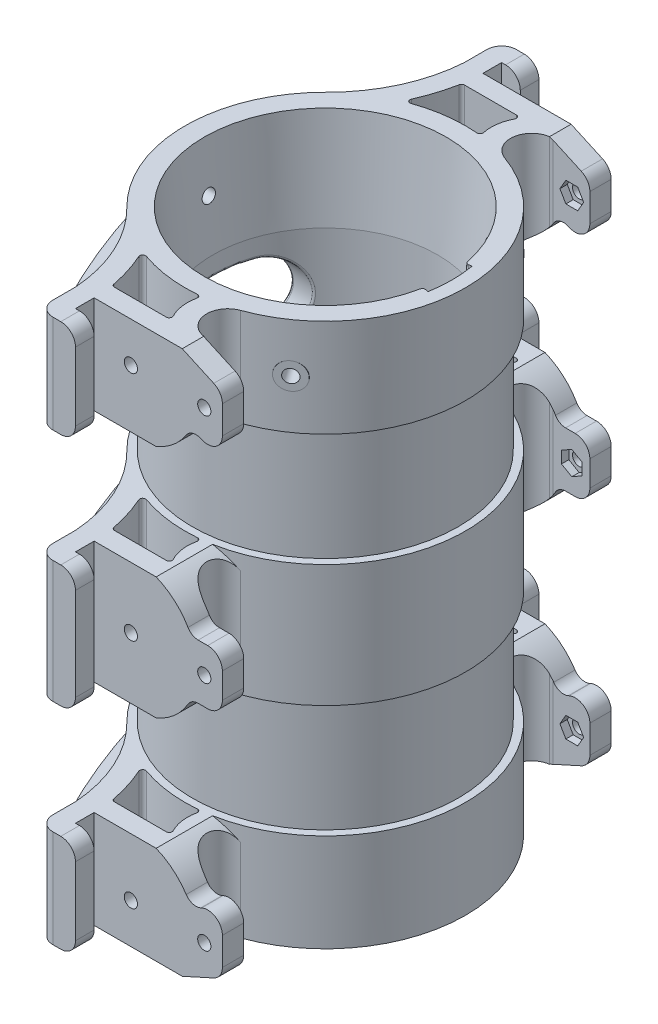
SolidWorks part; units mm, degrees
ref_plane "Front Plane" through (0, 0, 0) normal (0, 0, 1) x (1, 0, 0)
ref_plane "Top Plane" through (0, 0, 0) normal (0, 1, 0) x (1, 0, 0)
ref_plane "Right Plane" through (0, 0, 0) normal (1, 0, 0) x (0, 0, -1)
sketch "Sketch1" plane through (0, 0, 0) normal (0, 1, 0) x (1, 0, 0)
  line L0 (0, 38.25) -> (0, 45.25) construction
  circle A0 centre (0, 0) radius 38.25
  circle A1 centre (0, 0) radius 45.25
  dimension "D1" = 76.5
  dimension "D2" = 7
extrude "Boss-Extrude1" add sketch "Sketch1" along normal mid plane 185
sketch "Sketch2" plane through (0, -92.5, 0) normal (0, -1, 0) x (1, 0, 0)
  line L0 (0, 36.25) -> (0, 38.25) construction
  circle A0 centre (0, 0) radius 36.25
  circle A1 centre (0, 0) radius 38.25 construction
  circle A2 centre (0, 0) radius 38.25
  dimension "D1" = 2
extrude "Boss-Extrude2" add sketch "Sketch2" against normal blind 100 from offset 6.35 offset against normal yes
sketch "Sketch7" plane through (0, 0, 0) normal (1, 0, 0) x (0, 0, -1)
  line L0 (45.25, 92.5) -> (-45.25, 92.5) construction
  line L1 (12.5, 40) -> (-12.5, 40) construction
  line L2 (12.5, 27.5) -> (-12.5, 27.5)
  line L3 (12.5, 52.5) -> (-12.5, 52.5)
  circle A0 centre (0, 40) radius 12.5 construction
  arc A1 (12.5, 27.5) -> (12.5, 52.5) centre (12.5, 40) ccw
  arc A2 (-12.5, 52.5) -> (-12.5, 27.5) centre (-12.5, 40) ccw
  point P7 (0, 40)
  dimension "D2" = 25
  dimension "D3" = 25
  dimension "D1" = 52.5
extrude "Cut-Extrude4" cut sketch "Sketch7" against normal through all
sketch "Sketch8" plane through (0, 0, 0) normal (0, 1, 0) x (1, 0, 0)
  line L1 (17.5, -66.175) -> (128.1882, -66.175) construction
  line L2 (-18.85, -66.175) -> (-18.85, -78.875)
  line L3 (-18.85, -78.875) -> (-6.15, -78.875)
  line L4 (45.25, 0) -> (-45.25, 0) construction
  line L5 (31.75, 0) -> (50, 0) construction
  line L6 (-6.15, -78.875) -> (-6.15, -72.525)
  line L7 (-12.5, -72.525) -> (17.5, -72.525) construction
  line L8 (-6.15, -72.525) -> (-12.5, -72.525)
  line L9 (-12.5, -72.525) -> (-12.5, -66.175)
  line L10 (-12.5, -66.175) -> (43.65, -66.175)
  line L11 (-12.5, 66.175) -> (43.65, 66.175)
  line L12 (-12.5, 72.525) -> (-12.5, 66.175)
  line L13 (-6.15, 72.525) -> (-12.5, 72.525)
  line L14 (-6.15, 78.875) -> (-6.15, 72.525)
  line L15 (-18.85, 78.875) -> (-6.15, 78.875)
  line L16 (-18.85, 66.175) -> (-18.85, 78.875)
  line L18 (43.65, -66.175) -> (43.65, -58.9107)
  line L19 (43.65, -58.9107) -> (18.65, -58.9107)
  line L20 (43.65, 58.9107) -> (18.65, 58.9107)
  line L21 (43.65, 66.175) -> (43.65, 58.9107)
  line L22 (-12.5, -72.525) -> (-18.85, -72.525) construction
  arc A0 (-32.8241, -31.1471) -> (-18.85, -66.175) centre (-69.7381, -66.175) cw
  circle A1 centre (0, 0) radius 45.25 construction
  arc A2 (-32.8241, -31.1471) -> (15.7007, -42.4388) centre (0, 0) ccw
  arc A3 (-32.8241, 31.1471) -> (15.7007, 42.4388) centre (0, 0) cw
  arc A4 (-32.8241, 31.1471) -> (-18.85, 66.175) centre (-69.7381, 66.175) ccw
  arc A9 (18.65, -58.9107) -> (15.7007, -42.4388) centre (18.65, -50.4107) cw
  arc A10 (18.65, 58.9107) -> (15.7007, 42.4388) centre (18.65, 50.4107) ccw
  dimension "D1" = 8.5
  dimension "D2" = 62.5
  dimension "D3" = 25
extrude "Boss-Extrude3" add sketch "Sketch8" along normal up to surface and the other way up to surface up to face at (0, 92.5, 45.25) other way up to face at (0, -92.5, 45.25)
sketch "Sketch10" plane through (0, 0, 66.175) normal (0, 0, 1) x (1, 0, 0)
  line L0 (17.5, -92.5) -> (43.65, -92.5)
  line L1 (43.65, -92.5) -> (43.65, -80.6536)
  line L2 (-6.15, -59.2129) -> (-32.8241, -59.2129)
  line L3 (128.1882, -42.3564) -> (17.5, -92.5) construction
  line L4 (43.65, -80.6536) -> (17.5, -92.5)
  line L5 (43.65, 80.6536) -> (43.65, 92.5)
  line L6 (17.5, 92.5) -> (128.1882, 42.3564) construction
  line L7 (43.65, 92.5) -> (17.5, 92.5)
  line L8 (-12.5, 92.5) -> (43.65, 92.5) construction
  line L9 (17.5, 92.5) -> (43.65, 80.6536)
  line L10 (43.65, -60.1882) -> (43.65, -9.3209)
  line L11 (79.953, -43.7423) -> (23.8431, -69.161) construction
  line L12 (22.9086, -9.3209) -> (60.2886, -9.3209) construction
  line L21 (22.9086, -9.3209) -> (43.65, -9.3209)
  line L23 (43.65, -60.1882) -> (23.8431, -69.161)
  line L25 (-6.15, 92.5) -> (-6.15, -92.5) construction
  line L26 (-32.8241, 92.5) -> (-32.8241, -92.5) construction
  line L32 (-32.8241, -59.2129) -> (-32.8241, -20.7871)
  line L36 (-32.8241, -20.7871) -> (-6.15, -20.7871)
  line L40 (0, 0) -> (-32.8241, 0) construction
  line L45 (8.611, -59.2129) -> (-6.15, -59.2129)
  line L46 (8.611, -20.7871) -> (-6.15, -20.7871)
  line L47 (-32.8241, 59.2129) -> (-32.8241, 20.7871)
  line L48 (-6.15, 59.2129) -> (-32.8241, 59.2129)
  line L49 (8.611, 59.2129) -> (-6.15, 59.2129)
  line L50 (43.65, 60.1882) -> (23.8431, 69.161)
  line L51 (43.65, 60.1882) -> (43.65, 9.3209)
  line L52 (22.9086, 9.3209) -> (43.65, 9.3209)
  line L53 (8.611, 20.7871) -> (-6.15, 20.7871)
  line L54 (-32.8241, 20.7871) -> (-6.15, 20.7871)
  line L55 (43.65, 92.5) -> (43.65, -92.5) construction
  arc A6 (18.8427, -67.7035) -> (23.8431, -69.161) centre (22.1925, -65.5175) ccw construction
  arc A7 (18.8427, -67.7035) -> (8.611, -59.2129) centre (0, -80) ccw construction
  arc A10 (8.611, -20.7871) -> (19.4507, -11.3102) centre (0, 0) ccw construction
  arc A11 (22.9086, -9.3209) -> (19.4507, -11.3102) centre (22.9086, -13.3209) ccw construction
  arc A18 (18.8427, -67.7035) -> (23.8431, -69.161) centre (22.1925, -65.5175) ccw
  arc A19 (18.8427, -67.7035) -> (8.611, -59.2129) centre (0, -80) ccw
  arc A22 (8.611, -20.7871) -> (19.4507, -11.3102) centre (0, 0) ccw
  arc A23 (22.9086, -9.3209) -> (19.4507, -11.3102) centre (22.9086, -13.3209) ccw
  arc A24 (18.8427, 67.7035) -> (8.611, 59.2129) centre (0, 80) cw
  arc A25 (18.8427, 67.7035) -> (23.8431, 69.161) centre (22.1925, 65.5175) cw
  arc A26 (22.9086, 9.3209) -> (19.4507, 11.3102) centre (22.9086, 13.3209) cw
  arc A27 (8.611, 20.7871) -> (19.4507, 11.3102) centre (0, 0) cw
extrude "Cut-Extrude6" cut sketch "Sketch10" against normal up to surface and the other way through all up to face at (-41.5057, 40, 0)
sketch "Sketch11" plane through (0, 0, -78.875) normal (0, 0, -1) x (-1, 0, 0)
  line L3 (-43.65, 92.5) -> (-43.65, 80.6536)
  line L4 (-17.5, 92.5) -> (-43.65, 92.5)
  line L5 (-43.65, 80.6536) -> (-17.5, 92.5)
  line L6 (-43.65, 92.5) -> (-43.65, 80.6536)
  line L7 (-17.5, 92.5) -> (-43.65, 92.5)
  line L8 (-43.65, 80.6536) -> (-17.5, 92.5)
  line L9 (-43.65, -92.5) -> (-17.5, -92.5)
  line L10 (-43.65, -80.6536) -> (-43.65, -92.5)
  line L11 (-17.5, -92.5) -> (-43.65, -80.6536)
  line L12 (-43.65, -92.5) -> (-17.5, -92.5)
  line L13 (-43.65, -80.6536) -> (-43.65, -92.5)
  line L14 (-17.5, -92.5) -> (-43.65, -80.6536)
  line L20 (32.8241, 20.7871) -> (32.8241, 59.2129)
  line L21 (6.15, 20.7871) -> (32.8241, 20.7871)
  line L22 (-8.611, 20.7871) -> (6.15, 20.7871)
  line L23 (-43.65, 9.3209) -> (-22.9086, 9.3209)
  line L24 (-43.65, 60.1882) -> (-43.65, 9.3209)
  line L25 (-23.8431, 69.161) -> (-43.65, 60.1882)
  line L26 (6.15, 59.2129) -> (-8.611, 59.2129)
  line L27 (32.8241, 59.2129) -> (6.15, 59.2129)
  line L28 (32.8241, 20.7871) -> (32.8241, 59.2129)
  line L29 (6.15, 20.7871) -> (32.8241, 20.7871)
  line L30 (-8.611, 20.7871) -> (6.15, 20.7871)
  line L31 (-43.65, 9.3209) -> (-22.9086, 9.3209)
  line L32 (-43.65, 60.1882) -> (-43.65, 9.3209)
  line L33 (-23.8431, 69.161) -> (-43.65, 60.1882)
  line L34 (6.15, 59.2129) -> (-8.611, 59.2129)
  line L35 (32.8241, 59.2129) -> (6.15, 59.2129)
  line L36 (-22.9086, -9.3209) -> (-43.65, -9.3209)
  line L37 (-43.65, -9.3209) -> (-43.65, -60.1882)
  line L38 (-43.65, -60.1882) -> (-23.8431, -69.161)
  line L39 (-8.611, -59.2129) -> (6.15, -59.2129)
  line L40 (6.15, -59.2129) -> (32.8241, -59.2129)
  line L41 (32.8241, -59.2129) -> (32.8241, -20.7871)
  line L42 (32.8241, -20.7871) -> (6.15, -20.7871)
  line L43 (6.15, -20.7871) -> (-8.611, -20.7871)
  line L44 (-22.9086, -9.3209) -> (-43.65, -9.3209)
  line L45 (-43.65, -9.3209) -> (-43.65, -60.1882)
  line L46 (-43.65, -60.1882) -> (-23.8431, -69.161)
  line L47 (-8.611, -59.2129) -> (6.15, -59.2129)
  line L48 (6.15, -59.2129) -> (32.8241, -59.2129)
  line L49 (32.8241, -59.2129) -> (32.8241, -20.7871)
  line L50 (32.8241, -20.7871) -> (6.15, -20.7871)
  line L51 (6.15, -20.7871) -> (-8.611, -20.7871)
  arc A4 (-8.611, 20.7871) -> (-19.4507, 11.3102) centre (0, 0) ccw
  arc A5 (-22.9086, 9.3209) -> (-19.4507, 11.3102) centre (-22.9086, 13.3209) ccw
  arc A6 (-18.8427, 67.7035) -> (-23.8431, 69.161) centre (-22.1925, 65.5175) ccw
  arc A7 (-18.8427, 67.7035) -> (-8.611, 59.2129) centre (0, 80) ccw
  arc A8 (-8.611, 20.7871) -> (-19.4507, 11.3102) centre (0, 0) ccw
  arc A9 (-22.9086, 9.3209) -> (-19.4507, 11.3102) centre (-22.9086, 13.3209) ccw
  arc A10 (-18.8427, 67.7035) -> (-23.8431, 69.161) centre (-22.1925, 65.5175) ccw
  arc A11 (-18.8427, 67.7035) -> (-8.611, 59.2129) centre (0, 80) ccw
  arc A12 (-23.8431, -69.161) -> (-18.8427, -67.7035) centre (-22.1925, -65.5175) ccw
  arc A13 (-8.611, -59.2129) -> (-18.8427, -67.7035) centre (0, -80) ccw
  arc A14 (-19.4507, -11.3102) -> (-8.611, -20.7871) centre (0, 0) ccw
  arc A15 (-19.4507, -11.3102) -> (-22.9086, -9.3209) centre (-22.9086, -13.3209) ccw
  arc A16 (-23.8431, -69.161) -> (-18.8427, -67.7035) centre (-22.1925, -65.5175) ccw
  arc A17 (-8.611, -59.2129) -> (-18.8427, -67.7035) centre (0, -80) ccw
  arc A18 (-19.4507, -11.3102) -> (-8.611, -20.7871) centre (0, 0) ccw
  arc A19 (-19.4507, -11.3102) -> (-22.9086, -9.3209) centre (-22.9086, -13.3209) ccw
  dimension "D1" = 0
  dimension "D2" = 0
  dimension "D3" = 0
  dimension "D4" = 0
extrude "Cut-Extrude7" cut sketch "Sketch11" against normal up to surface (66.9486 mm away) up to face at (-3.9052, 0.3336, 17.6166)
fillet "Fillet5" radius 5 6 edges at (-18.85, -75.8565, -78.875) (-18.85, 0, -78.875) (-18.85, 75.8565, -78.875) (-18.85, 0, 78.875) (-18.85, -75.8565, 78.875) (-18.85, 75.8565, 78.875)
sketch "Sketch14" plane through (0, 0, -66.175) normal (0, 0, -1) x (-1, 0, 0)
  line L0 (0, 0) -> (-25, 0) construction
  line L5 (-25, 78.8696) -> (-25, 0) construction
  circle A3 centre (-25, 78.8696) radius 2.25
  circle A5 centre (-25, 0) radius 2.25
  circle A7 centre (-25, -78.8696) radius 2.25
  circle A8 centre (0, 0) radius 2.25
  circle A9 centre (0, 78.8696) radius 2.25
  circle A10 centre (0, -78.8696) radius 2.25
  dimension "D1" = 25
  dimension "D2" = 78.8696
  dimension "D3" = 4.5
extrude "Cut-Extrude8" cut sketch "Sketch14" against normal up to surface (7.2643 mm away) up to face at (27.8361, -73.0039, -58.9107)
sketch "Sketch15" plane through (0, 0, 66.175) normal (0, 0, 1) x (1, 0, 0)
  circle A1 centre (0, -78.8696) radius 2.25
  circle A3 centre (0, -78.8696) radius 2.25
  circle A5 centre (0, 78.8696) radius 2.25
  circle A7 centre (0, 78.8696) radius 2.25
  circle A9 centre (0, 0) radius 2.25
  circle A11 centre (0, 0) radius 2.25
  circle A13 centre (25, 78.8696) radius 2.25
  circle A14 centre (25, 78.8696) radius 2.25
  circle A15 centre (25, -78.8696) radius 2.25
  circle A16 centre (25, -78.8696) radius 2.25
  circle A17 centre (25, 0) radius 2.25
  circle A18 centre (25, 0) radius 2.25
  dimension "D1" = 0
  dimension "D2" = 0
  dimension "D3" = 0
  dimension "D4" = 0
  dimension "D5" = 0
  dimension "D6" = 0
extrude "Cut-Extrude9" cut sketch "Sketch15" against normal up to surface (7.2643 mm away) up to face at (27.8361, -73.0039, 58.9107)
sketch "Sketch16" plane through (0, 92.5, 0) normal (0, 1, 0) x (1, 0, 0)
  line L0 (-45.25, 0) -> (-47.75, 0) construction
  circle A0 centre (0, 0) radius 47.75
  circle A1 centre (0, 0) radius 45.25
  arc A2 (-32.8241, 31.1471) -> (-32.8241, -31.1471) centre (0, 0) ccw construction
  dimension "D1" = 2.5
extrude "Boss-Extrude4" add sketch "Sketch16" against normal up to surface (33.2871 mm away) up to face at (-10.3824, 59.2129, 65.577)
sketch "Sketch17" plane through (0, -92.5, 0) normal (0, -1, 0) x (1, 0, 0)
  circle A1 centre (0, 0) radius 45.25
  circle A2 centre (0, 0) radius 45.25
  circle A3 centre (0, 0) radius 47.75
  circle A4 centre (0, 0) radius 47.75
  dimension "D1" = 0
  dimension "D2" = 0
extrude "Boss-Extrude5" add sketch "Sketch17" against normal up to surface (33.2871 mm away) up to face at (-10.3824, -59.2129, 65.577)
sketch "Sketch18" plane through (0, -20.7871, 0) normal (0, -1, 0) x (1, 0, 0)
  circle A1 centre (0, 0) radius 47.75
  circle A2 centre (0, 0) radius 47.75
  circle A3 centre (0, 0) radius 45.25
  circle A4 centre (0, 0) radius 45.25
  dimension "D1" = 0
  dimension "D2" = 0
extrude "Boss-Extrude6" add sketch "Sketch18" against normal up to surface (41.5741 mm away) up to face at (-10.3824, 20.7871, 65.577)
sketch "Sketch20" plane through (0, 0, 0) normal (1, 0, 0) x (0, 0, -1)
  line L0 (-45.25, -20.7871) -> (45.25, -20.7871) construction
  line L1 (46.9672, -59.2129) -> (-46.9672, -59.2129) construction
  line L2 (-45.25, 59.2129) -> (45.25, 59.2129) construction
  line L3 (46.9672, 20.7871) -> (-46.9672, 20.7871) construction
  line L4 (-45.25, -20.7871) -> (45.25, -20.7871) construction
  line L5 (46.9672, -59.2129) -> (-46.9672, -59.2129) construction
  line L6 (-45.25, 59.2129) -> (45.25, 59.2129) construction
  line L7 (46.9672, 20.7871) -> (-46.9672, 20.7871) construction
  line L8 (0, -20.7871) -> (0, -59.2129) construction
  line L9 (0, 59.2129) -> (0, 20.7871) construction
  line L10 (-10, 40) -> (10, 40) construction
  line L11 (-10, 45) -> (10, 45)
  line L12 (-10, 35) -> (10, 35)
  line L13 (0, 0) -> (46.4328, 0) construction
  line L14 (46.4328, 19.5496) -> (46.4328, -19.5496) construction
  line L15 (-10, -40) -> (10, -40) construction
  line L16 (-10, -45) -> (10, -45)
  line L17 (-10, -35) -> (10, -35)
  arc A2 (-10, 45) -> (-10, 35) centre (-10, 40) ccw
  arc A3 (10, 35) -> (10, 45) centre (10, 40) ccw
  arc A4 (-10, -45) -> (-10, -35) centre (-10, -40) cw
  arc A5 (10, -35) -> (10, -45) centre (10, -40) cw
  point P2 (0, 40)
  point P14 (0, -20.7871)
  point P30 (0, -40)
  dimension "D1" = 20
  dimension "D2" = 5
extrude "Cut-Extrude10" [suppressed] cut sketch "Sketch20" along normal through all
pattern_circular "CirPattern1" [suppressed] count 6 over 360 reverse direction yes of bodies 118
ref_plane "Plane1" through (-26.1107, -92.5, 39.9787) normal (0, -1, 0) x (-1, 0, 0)
sketch "Sketch23" plane through (0, -92.5, 0) normal (0, -1, 0) x (1, 0, 0)
  line L0 (0, 0) -> (-47.75, 0) construction
  arc A0 (-18.85, 66.175) -> (-33.5786, 33.9491) centre (-68.7395, 69.4978) cw
  arc A1 (-26.1107, 39.9787) -> (-26.1107, -39.9787) centre (0, 0) ccw construction
  arc A2 (-33.5786, 33.9491) -> (-26.1107, 39.9787) centre (0, 0) cw
  arc A3 (-18.85, 66.175) -> (-26.1107, 39.9787) centre (-69.7381, 66.175) cw
  arc A4 (-18.85, -66.175) -> (-26.1107, -39.9787) centre (-69.7381, -66.175) ccw
  arc A5 (-33.5786, -33.9491) -> (-26.1107, -39.9787) centre (0, 0) ccw
  arc A6 (-18.85, -66.175) -> (-33.5786, -33.9491) centre (-68.7395, -69.4978) ccw
  arc A7 (-26.1107, 39.9787) -> (-18.85, 66.175) centre (-69.7381, 66.175) ccw construction
  dimension "D1" = 50
extrude "Boss-Extrude7" add sketch "Sketch23" against normal up to surface (33.2871 mm away) up to face at (-8.8243, -59.2129, 0)
sketch "Sketch24" plane through (0, 92.5, 0) normal (0, 1, 0) x (1, 0, 0)
  arc A3 (-26.1107, 39.9787) -> (-18.85, 66.175) centre (-69.7381, 66.175) ccw
  arc A4 (-26.1107, 39.9787) -> (-33.5786, 33.9491) centre (0, 0) ccw
  arc A5 (-33.5786, 33.9491) -> (-18.85, 66.175) centre (-68.7395, 69.4978) ccw
  arc A6 (-26.1107, 39.9787) -> (-18.85, 66.175) centre (-69.7381, 66.175) ccw
  arc A7 (-26.1107, 39.9787) -> (-33.5786, 33.9491) centre (0, 0) ccw
  arc A8 (-33.5786, 33.9491) -> (-18.85, 66.175) centre (-68.7395, 69.4978) ccw
  arc A9 (-18.85, -66.175) -> (-33.5786, -33.9491) centre (-68.7395, -69.4978) ccw
  arc A10 (-33.5786, -33.9491) -> (-26.1107, -39.9787) centre (0, 0) ccw
  arc A11 (-18.85, -66.175) -> (-26.1107, -39.9787) centre (-69.7381, -66.175) ccw
  arc A12 (-18.85, -66.175) -> (-33.5786, -33.9491) centre (-68.7395, -69.4978) ccw
  arc A13 (-33.5786, -33.9491) -> (-26.1107, -39.9787) centre (0, 0) ccw
  arc A14 (-18.85, -66.175) -> (-26.1107, -39.9787) centre (-69.7381, -66.175) ccw
  dimension "D1" = 0
  dimension "D2" = 0
extrude "Boss-Extrude8" add sketch "Sketch24" against normal up to surface (33.2871 mm away) up to face at (-45.25, 59.2129, 0)
sketch "Sketch25" plane through (0, 20.7871, 0) normal (0, 1, 0) x (1, 0, 0)
  arc A3 (-18.85, -66.175) -> (-33.5786, -33.9491) centre (-68.7395, -69.4978) ccw
  arc A4 (-33.5786, -33.9491) -> (-26.1107, -39.9787) centre (0, 0) ccw
  arc A5 (-18.85, -66.175) -> (-26.1107, -39.9787) centre (-69.7381, -66.175) ccw
  arc A6 (-18.85, -66.175) -> (-33.5786, -33.9491) centre (-68.7395, -69.4978) ccw
  arc A7 (-33.5786, -33.9491) -> (-26.1107, -39.9787) centre (0, 0) ccw
  arc A8 (-18.85, -66.175) -> (-26.1107, -39.9787) centre (-69.7381, -66.175) ccw
  arc A9 (-26.1107, 39.9787) -> (-18.85, 66.175) centre (-69.7381, 66.175) ccw
  arc A10 (-33.5786, 33.9491) -> (-18.85, 66.175) centre (-68.7395, 69.4978) ccw
  arc A11 (-26.1107, 39.9787) -> (-33.5786, 33.9491) centre (0, 0) ccw
  arc A12 (-26.1107, 39.9787) -> (-18.85, 66.175) centre (-69.7381, 66.175) ccw
  arc A13 (-33.5786, 33.9491) -> (-18.85, 66.175) centre (-68.7395, 69.4978) ccw
  arc A14 (-26.1107, 39.9787) -> (-33.5786, 33.9491) centre (0, 0) ccw
  dimension "D1" = 0
  dimension "D2" = 0
extrude "Boss-Extrude9" add sketch "Sketch25" against normal up to surface (41.5741 mm away) up to face at (-45.25, -20.7871, 0)
sketch "Sketch27" plane through (0, 0, 0) normal (0, 0, 1) x (1, 0, 0)
  line L0 (38.25, 59.2129) -> (41.1622, 92.5)
  line L3 (38.25, 59.2129) -> (0, 59.2129) construction
  line L5 (-18.85, 92.5) -> (-33.5786, 92.5) construction
  line L6 (38.25, 59.2129) -> (38.25, 92.5)
  line L7 (38.25, 92.5) -> (41.1622, 92.5)
  line L8 (0, 59.2129) -> (0, 92.5) construction
  dimension "D1" = 33.2871
  dimension "D2" = 5
  dimension "D3" = 38.25
  dimension "D4" = 38.25
  dimension "D5" = 38.25
revolve "Cut-Revolve1" cut sketch "Sketch27" angle 360 about L8
sketch "Sketch28" plane through (0, 92.5, 0) normal (0, 1, 0) x (1, 0, 0)
  line L1 (43.65, 58.9107) -> (18.65, 58.9107) construction
  line L2 (0, 0) -> (47.75, 0) construction
  line L3 (11.1383, 46.4328) -> (10.15, 46.6698)
  line L4 (10.15, 46.6698) -> (10.15, 58.8326)
  line L5 (10.15, 58.8326) -> (17.5, 58.8326)
  line L6 (10.15, -58.8326) -> (17.5, -58.8326)
  line L7 (10.15, -46.6698) -> (10.15, -58.8326)
  line L8 (11.1383, -46.4328) -> (10.15, -46.6698)
  arc A0 (17.5, 58.8326) -> (16.1276, 44.944) centre (18.5576, 51.716) ccw
  arc A1 (11.1383, -46.4328) -> (11.1383, 46.4328) centre (0, 0) ccw construction
  arc A2 (16.1276, 44.944) -> (11.1383, 46.4328) centre (0, 0) ccw
  arc A7 (17.5, 58.8326) -> (11.1383, 46.4328) centre (18.65, 50.4107) ccw construction
  arc A8 (16.1276, -44.944) -> (11.1383, -46.4328) centre (0, 0) cw
  arc A9 (17.5, -58.8326) -> (16.1276, -44.944) centre (18.5576, -51.716) cw
extrude "Boss-Extrude13" add sketch "Sketch28" against normal up to surface (26.6421 mm away) up to face at (13.4579, 62.8457, 57.713)
sketch "Sketch29" plane through (0, -92.5, 0) normal (0, -1, 0) x (1, 0, 0)
  line L3 (11.1383, -46.4328) -> (10.15, -46.6698)
  line L4 (10.15, -46.6698) -> (10.15, -58.8326)
  line L5 (10.15, -58.8326) -> (17.5, -58.8326)
  line L6 (11.1383, -46.4328) -> (10.15, -46.6698)
  line L7 (10.15, -46.6698) -> (10.15, -58.8326)
  line L8 (10.15, -58.8326) -> (17.5, -58.8326)
  line L9 (17.5, 58.8326) -> (10.15, 58.8326)
  line L10 (10.15, 46.6698) -> (11.1383, 46.4328)
  line L11 (10.15, 58.8326) -> (10.15, 46.6698)
  line L12 (17.5, 58.8326) -> (10.15, 58.8326)
  line L13 (10.15, 46.6698) -> (11.1383, 46.4328)
  line L14 (10.15, 58.8326) -> (10.15, 46.6698)
  arc A2 (16.1276, -44.944) -> (17.5, -58.8326) centre (18.5576, -51.716) ccw
  arc A3 (11.1383, -46.4328) -> (16.1276, -44.944) centre (0, 0) ccw
  arc A4 (16.1276, -44.944) -> (17.5, -58.8326) centre (18.5576, -51.716) ccw
  arc A5 (11.1383, -46.4328) -> (16.1276, -44.944) centre (0, 0) ccw
  arc A6 (17.5, 58.8326) -> (16.1276, 44.944) centre (18.5576, 51.716) ccw
  arc A7 (16.1276, 44.944) -> (11.1383, 46.4328) centre (0, 0) ccw
  arc A8 (17.5, 58.8326) -> (16.1276, 44.944) centre (18.5576, 51.716) ccw
  arc A9 (16.1276, 44.944) -> (11.1383, 46.4328) centre (0, 0) ccw
  dimension "D1" = 0
  dimension "D2" = 0
extrude "Boss-Extrude14" add sketch "Sketch29" against normal up to surface (32.0496 mm away) up to face at (13.7418, -62.9735, 57.3608)
sketch "Sketch30" plane through (0, 0, 0) normal (0, 1, 0) x (1, 0, 0)
  line L3 (10.15, 46.6698) -> (11.1383, 46.4328)
  line L4 (10.15, 58.8326) -> (10.15, 46.6698)
  line L5 (17.5, 58.8326) -> (10.15, 58.8326)
  line L6 (10.15, 46.6698) -> (11.1383, 46.4328)
  line L7 (10.15, 58.8326) -> (10.15, 46.6698)
  line L8 (17.5, 58.8326) -> (10.15, 58.8326)
  line L9 (10.15, -46.6698) -> (10.15, -58.8326)
  line L10 (10.15, -58.8326) -> (17.5, -58.8326)
  line L11 (11.1383, -46.4328) -> (10.15, -46.6698)
  line L12 (10.15, -46.6698) -> (10.15, -58.8326)
  line L13 (10.15, -58.8326) -> (17.5, -58.8326)
  line L14 (11.1383, -46.4328) -> (10.15, -46.6698)
  arc A2 (17.5, 58.8326) -> (16.1276, 44.944) centre (18.5576, 51.716) ccw
  arc A3 (16.1276, 44.944) -> (11.1383, 46.4328) centre (0, 0) ccw
  arc A4 (17.5, 58.8326) -> (16.1276, 44.944) centre (18.5576, 51.716) ccw
  arc A5 (16.1276, 44.944) -> (11.1383, 46.4328) centre (0, 0) ccw
  arc A6 (16.1276, -44.944) -> (17.5, -58.8326) centre (18.5576, -51.716) ccw
  arc A7 (11.1383, -46.4328) -> (16.1276, -44.944) centre (0, 0) ccw
  arc A8 (16.1276, -44.944) -> (17.5, -58.8326) centre (18.5576, -51.716) ccw
  arc A9 (11.1383, -46.4328) -> (16.1276, -44.944) centre (0, 0) ccw
  dimension "D1" = 0
  dimension "D2" = 0
extrude "Boss-Extrude15" add sketch "Sketch30" against normal up to surface and the other way up to surface up to face at (13.9691, -16.7184, -57.3608) other way up to face at (13.6851, 16.8462, -57.713)
ref_plane "Plane2" through (0, 75.8565, 0) normal (0, 1, 0) x (1, 0, 0)
sketch "Sketch31" plane through (0, 75.8565, 0) normal (0, 1, 0) x (1, 0, 0)
  line L0 (0, 0) -> (27.3883, 39.1145) construction
  line L1 (0, 0) -> (-47.75, 0) construction
  arc A0 (16.1276, -44.944) -> (16.1276, 44.944) centre (0, 0) ccw construction
  arc A1 (-33.5786, 33.9491) -> (-33.5786, -33.9491) centre (0, 0) ccw construction
  dimension "D1" = 125
ref_plane "Plane3" through (27.3883, 75.8565, -39.1145) normal (0.5736, 0, -0.8192) x (-0.8192, 0, -0.5736)
sketch "Sketch34" plane through (0, 75.8565, 0) normal (0, 1, 0) x (1, 0, 0)
  line L1 (-18.85, 66.175) -> (-18.85, 73.875)
  line L2 (0, 0) -> (-47.75, 0) construction
  line L4 (-18.85, -66.175) -> (-18.85, -73.875)
  arc A0 (-13.85, 78.875) -> (-18.85, 73.875) centre (-13.85, 73.875) ccw construction
  arc A2 (-46.2179, 11.9988) -> (-33.5786, 33.9491) centre (0, 0) cw
  arc A3 (-33.5786, 33.9491) -> (-18.85, 66.175) centre (-68.7395, 69.4978) ccw
  arc A4 (-18.85, 73.875) -> (-18.0639, 76.5663) centre (-13.85, 73.875) cw
  arc A10 (-33.5786, 33.9491) -> (-33.5786, -33.9491) centre (0, 0) ccw construction
  arc A11 (-46.2179, 11.9988) -> (-18.0639, 76.5663) centre (171.5626, -44.5402) cw
  arc A12 (-33.5786, 33.9491) -> (-18.85, 66.175) centre (-68.7395, 69.4978) ccw construction
  arc A13 (-46.2179, -11.9988) -> (-18.0639, -76.5663) centre (171.5626, 44.5402) ccw
  arc A14 (-18.85, -73.875) -> (-18.0639, -76.5663) centre (-13.85, -73.875) ccw
  arc A15 (-33.5786, -33.9491) -> (-18.85, -66.175) centre (-68.7395, -69.4978) cw
  arc A16 (-46.2179, -11.9988) -> (-33.5786, -33.9491) centre (0, 0) ccw
  dimension "D1" = 225
extrude "Boss-Extrude17" add sketch "Sketch34" along normal mid plane 10
ref_plane "Plane4" through (0, 0, 0) normal (0, -1, 0) x (-1, 0, 0)
ref_plane "Plane5" through (0, -75.8565, 0) normal (0, -1, 0) x (-1, 0, 0)
sketch "Sketch35" plane through (0, 0, 0) normal (0, -1, 0) x (-1, 0, 0)
  line L1 (18.85, 73.875) -> (18.85, 66.175)
  line L2 (18.85, 73.875) -> (18.85, 66.175)
  line L3 (18.85, -66.175) -> (18.85, -73.875)
  line L4 (18.85, -66.175) -> (18.85, -73.875)
  arc A4 (46.2179, 11.9988) -> (18.0639, 76.5663) centre (-171.5626, -44.5402) ccw
  arc A5 (18.85, 73.875) -> (18.0639, 76.5663) centre (13.85, 73.875) ccw
  arc A6 (18.85, 66.175) -> (33.5786, 33.9491) centre (68.7395, 69.4978) ccw
  arc A7 (46.2179, 11.9988) -> (33.5786, 33.9491) centre (0, 0) ccw
  arc A8 (46.2179, 11.9988) -> (18.0639, 76.5663) centre (-171.5626, -44.5402) ccw
  arc A9 (18.85, 73.875) -> (18.0639, 76.5663) centre (13.85, 73.875) ccw
  arc A10 (18.85, 66.175) -> (33.5786, 33.9491) centre (68.7395, 69.4978) ccw
  arc A11 (46.2179, 11.9988) -> (33.5786, 33.9491) centre (0, 0) ccw
  arc A12 (18.0639, -76.5663) -> (18.85, -73.875) centre (13.85, -73.875) ccw
  arc A13 (18.0639, -76.5663) -> (46.2179, -11.9988) centre (-171.5626, 44.5402) ccw
  arc A14 (33.5786, -33.9491) -> (46.2179, -11.9988) centre (0, 0) ccw
  arc A15 (33.5786, -33.9491) -> (18.85, -66.175) centre (68.7395, -69.4978) ccw
  arc A16 (18.0639, -76.5663) -> (18.85, -73.875) centre (13.85, -73.875) ccw
  arc A17 (18.0639, -76.5663) -> (46.2179, -11.9988) centre (-171.5626, 44.5402) ccw
  arc A18 (33.5786, -33.9491) -> (46.2179, -11.9988) centre (0, 0) ccw
  arc A19 (33.5786, -33.9491) -> (18.85, -66.175) centre (68.7395, -69.4978) ccw
  dimension "D1" = 0
  dimension "D2" = 0
extrude "Boss-Extrude18" add sketch "Sketch35" along normal mid plane 10
sketch "Sketch36" plane through (0, -75.8565, 0) normal (0, -1, 0) x (-1, 0, 0)
  line L1 (18.85, 73.875) -> (18.85, 66.175)
  line L2 (18.85, 73.875) -> (18.85, 66.175)
  line L3 (18.85, -66.175) -> (18.85, -73.875)
  line L4 (18.85, -66.175) -> (18.85, -73.875)
  arc A4 (46.2179, 11.9988) -> (18.0639, 76.5663) centre (-171.5626, -44.5402) ccw
  arc A5 (18.85, 73.875) -> (18.0639, 76.5663) centre (13.85, 73.875) ccw
  arc A6 (18.85, 66.175) -> (33.5786, 33.9491) centre (68.7395, 69.4978) ccw
  arc A7 (46.2179, 11.9988) -> (33.5786, 33.9491) centre (0, 0) ccw
  arc A8 (46.2179, 11.9988) -> (18.0639, 76.5663) centre (-171.5626, -44.5402) ccw
  arc A9 (18.85, 73.875) -> (18.0639, 76.5663) centre (13.85, 73.875) ccw
  arc A10 (18.85, 66.175) -> (33.5786, 33.9491) centre (68.7395, 69.4978) ccw
  arc A11 (46.2179, 11.9988) -> (33.5786, 33.9491) centre (0, 0) ccw
  arc A12 (18.0639, -76.5663) -> (18.85, -73.875) centre (13.85, -73.875) ccw
  arc A13 (18.0639, -76.5663) -> (46.2179, -11.9988) centre (-171.5626, 44.5402) ccw
  arc A14 (33.5786, -33.9491) -> (46.2179, -11.9988) centre (0, 0) ccw
  arc A15 (33.5786, -33.9491) -> (18.85, -66.175) centre (68.7395, -69.4978) ccw
  arc A16 (18.0639, -76.5663) -> (18.85, -73.875) centre (13.85, -73.875) ccw
  arc A17 (18.0639, -76.5663) -> (46.2179, -11.9988) centre (-171.5626, 44.5402) ccw
  arc A18 (33.5786, -33.9491) -> (46.2179, -11.9988) centre (0, 0) ccw
  arc A19 (33.5786, -33.9491) -> (18.85, -66.175) centre (68.7395, -69.4978) ccw
  dimension "D1" = 0
  dimension "D2" = 0
extrude "Boss-Extrude19" add sketch "Sketch36" along normal mid plane 10
sketch "Sketch32" plane through (27.3883, 75.8565, -39.1145) normal (0.5736, 0, -0.8192) x (-0.8192, 0, -0.5736)
  circle A0 centre (0, 0) radius 4.5
  dimension "D1" = 9
extrude "Boss-Extrude16" add sketch "Sketch32" against normal blind 1
sketch "Sketch33" plane through (27.3883, 0, -39.1145) normal (0.5736, 0, -0.8192) x (-0.8192, 0, -0.5736)
  circle A0 centre (0, 75.8565) radius 2.25
  dimension "D1" = 4.5
extrude "Cut-Extrude11" cut sketch "Sketch33" against normal up to surface (8.1077 mm away) up to face at (0, 92.5, -41.1622)
pattern_circular "CirPattern2" count 3 over 250 about axis through (0, -75.8444, 0) along (0, 1, 0) of "Boss-Extrude16", "Cut-Extrude11"
sketch "Sketch37" plane through (0, 0, 58.9107) normal (0, 0, -1) x (-1, 0, 0)
  line L1 (-2.0207, -3.5) -> (2.0207, -3.5)
  line L2 (2.0207, -3.5) -> (4.0415, 0)
  line L3 (4.0415, 0) -> (2.0207, 3.5)
  line L4 (2.0207, 3.5) -> (-2.0207, 3.5)
  line L5 (-2.0207, 3.5) -> (-4.0415, 0)
  line L6 (-4.0415, 0) -> (-2.0207, -3.5)
  line L13 (-28.5, 2.0207) -> (-28.5, -2.0207)
  line L14 (-28.5, -2.0207) -> (-25, -4.0415)
  line L15 (-25, -4.0415) -> (-21.5, -2.0207)
  line L16 (-21.5, -2.0207) -> (-21.5, 2.0207)
  line L17 (-21.5, 2.0207) -> (-25, 4.0415)
  line L18 (-25, 4.0415) -> (-28.5, 2.0207)
  line L25 (-29.0415, -78.8696) -> (-27.0207, -82.3696)
  line L26 (-27.0207, -82.3696) -> (-22.9793, -82.3696)
  line L27 (-22.9793, -82.3696) -> (-20.9585, -78.8696)
  line L28 (-20.9585, -78.8696) -> (-22.9793, -75.3696)
  line L29 (-22.9793, -75.3696) -> (-27.0207, -75.3696)
  line L30 (-27.0207, -75.3696) -> (-29.0415, -78.8696)
  line L37 (-2.0207, -82.3696) -> (2.0207, -82.3696)
  line L38 (2.0207, -82.3696) -> (4.0415, -78.8696)
  line L39 (4.0415, -78.8696) -> (2.0207, -75.3696)
  line L40 (2.0207, -75.3696) -> (-2.0207, -75.3696)
  line L41 (-2.0207, -75.3696) -> (-4.0415, -78.8696)
  line L42 (-4.0415, -78.8696) -> (-2.0207, -82.3696)
  line L43 (-2.0207, 75.3696) -> (2.0207, 75.3696)
  line L44 (2.0207, 75.3696) -> (4.0415, 78.8696)
  line L45 (4.0415, 78.8696) -> (2.0207, 82.3696)
  line L46 (2.0207, 82.3696) -> (-2.0207, 82.3696)
  line L47 (-2.0207, 82.3696) -> (-4.0415, 78.8696)
  line L48 (-4.0415, 78.8696) -> (-2.0207, 75.3696)
  line L49 (-27.0207, 75.3696) -> (-22.9793, 75.3696)
  line L50 (-22.9793, 75.3696) -> (-20.9585, 78.8696)
  line L51 (-20.9585, 78.8696) -> (-22.9793, 82.3696)
  line L52 (-22.9793, 82.3696) -> (-27.0207, 82.3696)
  line L53 (-27.0207, 82.3696) -> (-29.0415, 78.8696)
  line L54 (-29.0415, 78.8696) -> (-27.0207, 75.3696)
  circle A1 centre (-25, -78.8696) radius 2.25 construction
  circle A3 centre (-25, 0) radius 2.25 construction
  circle A5 centre (0, 0) radius 2.25 construction
  circle A7 centre (-25, -78.8696) radius 2.25 construction
  circle A9 centre (-25, 0) radius 2.25 construction
  circle A11 centre (0, 0) radius 2.25 construction
  circle A12 centre (0, 0) radius 3.5 construction
  circle A13 centre (0, 78.8696) radius 2.25 construction
  circle A14 centre (-25, 0) radius 3.5 construction
  circle A15 centre (-25, 78.8696) radius 2.25 construction
  circle A16 centre (-25, -78.8696) radius 3.5 construction
  circle A17 centre (0, -78.8696) radius 2.25 construction
  circle A18 centre (0, 78.8696) radius 2.25 construction
  circle A19 centre (-25, 78.8696) radius 2.25 construction
  circle A20 centre (0, -78.8696) radius 2.25 construction
  circle A21 centre (0, -78.8696) radius 3.5 construction
  circle A22 centre (0, 78.8696) radius 3.5 construction
  circle A23 centre (-25, 78.8696) radius 3.5 construction
  dimension "D2" = 7
  dimension "D3" = 4.0415
extrude "Cut-Extrude12" cut sketch "Sketch37" against normal blind 2.5
sketch "Sketch39" plane through (0, 0, -58.9107) normal (0, 0, 1) x (1, 0, 0)
  line L78 (-2.0207, -82.3696) -> (2.0207, -82.3696)
  line L79 (-4.0415, -78.8696) -> (-2.0207, -82.3696)
  line L80 (-2.0207, -75.3696) -> (-4.0415, -78.8696)
  line L81 (2.0207, -75.3696) -> (-2.0207, -75.3696)
  line L82 (4.0415, -78.8696) -> (2.0207, -75.3696)
  line L83 (2.0207, -82.3696) -> (4.0415, -78.8696)
  line L84 (-2.0207, -82.3696) -> (2.0207, -82.3696)
  line L85 (-4.0415, -78.8696) -> (-2.0207, -82.3696)
  line L86 (-2.0207, -75.3696) -> (-4.0415, -78.8696)
  line L87 (2.0207, -75.3696) -> (-2.0207, -75.3696)
  line L88 (4.0415, -78.8696) -> (2.0207, -75.3696)
  line L89 (2.0207, -82.3696) -> (4.0415, -78.8696)
  line L90 (-2.0207, -3.5) -> (2.0207, -3.5)
  line L91 (-4.0415, 0) -> (-2.0207, -3.5)
  line L92 (-2.0207, 3.5) -> (-4.0415, 0)
  line L93 (2.0207, 3.5) -> (-2.0207, 3.5)
  line L94 (4.0415, 0) -> (2.0207, 3.5)
  line L95 (2.0207, -3.5) -> (4.0415, 0)
  line L96 (-2.0207, -3.5) -> (2.0207, -3.5)
  line L97 (-4.0415, 0) -> (-2.0207, -3.5)
  line L98 (-2.0207, 3.5) -> (-4.0415, 0)
  line L99 (2.0207, 3.5) -> (-2.0207, 3.5)
  line L100 (4.0415, 0) -> (2.0207, 3.5)
  line L101 (2.0207, -3.5) -> (4.0415, 0)
  line L102 (-2.0207, 75.3696) -> (2.0207, 75.3696)
  line L103 (-4.0415, 78.8696) -> (-2.0207, 75.3696)
  line L104 (-2.0207, 82.3696) -> (-4.0415, 78.8696)
  line L105 (2.0207, 82.3696) -> (-2.0207, 82.3696)
  line L106 (4.0415, 78.8696) -> (2.0207, 82.3696)
  line L107 (2.0207, 75.3696) -> (4.0415, 78.8696)
  line L108 (-2.0207, 75.3696) -> (2.0207, 75.3696)
  line L109 (-4.0415, 78.8696) -> (-2.0207, 75.3696)
  line L110 (-2.0207, 82.3696) -> (-4.0415, 78.8696)
  line L111 (2.0207, 82.3696) -> (-2.0207, 82.3696)
  line L112 (4.0415, 78.8696) -> (2.0207, 82.3696)
  line L113 (2.0207, 75.3696) -> (4.0415, 78.8696)
  line L114 (28.5, -2.0207) -> (28.5, 2.0207)
  line L115 (25, -4.0415) -> (28.5, -2.0207)
  line L116 (21.5, -2.0207) -> (25, -4.0415)
  line L117 (21.5, 2.0207) -> (21.5, -2.0207)
  line L118 (25, 4.0415) -> (21.5, 2.0207)
  line L119 (28.5, 2.0207) -> (25, 4.0415)
  line L120 (28.5, -2.0207) -> (28.5, 2.0207)
  line L121 (25, -4.0415) -> (28.5, -2.0207)
  line L122 (21.5, -2.0207) -> (25, -4.0415)
  line L123 (21.5, 2.0207) -> (21.5, -2.0207)
  line L124 (25, 4.0415) -> (21.5, 2.0207)
  line L125 (28.5, 2.0207) -> (25, 4.0415)
  line L126 (22.9793, 75.3696) -> (27.0207, 75.3696)
  line L127 (20.9585, 78.8696) -> (22.9793, 75.3696)
  line L128 (22.9793, 82.3696) -> (20.9585, 78.8696)
  line L129 (27.0207, 82.3696) -> (22.9793, 82.3696)
  line L130 (29.0415, 78.8696) -> (27.0207, 82.3696)
  line L131 (27.0207, 75.3696) -> (29.0415, 78.8696)
  line L132 (22.9793, 75.3696) -> (27.0207, 75.3696)
  line L133 (20.9585, 78.8696) -> (22.9793, 75.3696)
  line L134 (22.9793, 82.3696) -> (20.9585, 78.8696)
  line L135 (27.0207, 82.3696) -> (22.9793, 82.3696)
  line L136 (29.0415, 78.8696) -> (27.0207, 82.3696)
  line L137 (27.0207, 75.3696) -> (29.0415, 78.8696)
  line L138 (22.9793, -82.3696) -> (27.0207, -82.3696)
  line L139 (20.9585, -78.8696) -> (22.9793, -82.3696)
  line L140 (22.9793, -75.3696) -> (20.9585, -78.8696)
  line L141 (27.0207, -75.3696) -> (22.9793, -75.3696)
  line L142 (29.0415, -78.8696) -> (27.0207, -75.3696)
  line L143 (27.0207, -82.3696) -> (29.0415, -78.8696)
  line L144 (22.9793, -82.3696) -> (27.0207, -82.3696)
  line L145 (20.9585, -78.8696) -> (22.9793, -82.3696)
  line L146 (22.9793, -75.3696) -> (20.9585, -78.8696)
  line L147 (27.0207, -75.3696) -> (22.9793, -75.3696)
  line L148 (29.0415, -78.8696) -> (27.0207, -75.3696)
  line L149 (27.0207, -82.3696) -> (29.0415, -78.8696)
  dimension "D1" = 0
  dimension "D2" = 0
  dimension "D3" = 0
  dimension "D4" = 0
  dimension "D5" = 0
  dimension "D6" = 0
extrude "Cut-Extrude13" cut sketch "Sketch39" against normal blind 2.5
sketch "Sketch44" plane through (0, 0, 0) normal (0, 0, 1) x (1, 0, 0)
  line L0 (41.1622, 92.5) -> (-41.1622, 92.5) construction
  line L1 (41.1622, 92.5) -> (-41.1622, 92.5) construction
  line L2 (41.1622, 92.5) -> (43.1622, 92.5)
  line L3 (38.25, 59.2129) -> (-38.25, 59.2129) construction
  line L4 (38.25, 59.2129) -> (-38.25, 59.2129) construction
  line L5 (38.25, 59.2129) -> (40.25, 59.2129)
  line L6 (40.25, 59.2129) -> (43.1622, 92.5)
  line L7 (38.25, 59.2129) -> (41.1622, 92.5)
  line L8 (0, 59.2129) -> (0, 92.5) construction
  dimension "D1" = 2
revolve "Cut-Revolve2" cut sketch "Sketch44" angle 10 about L8 other way angle 10
fillet "Fillet6" radius 1 2 edges at (39.1029, 75.8565, -6.8949) (39.1029, 75.8565, 6.8949)
sketch "Sketch45" plane through (0, 92.5, 0) normal (0, 1, 0) x (1, 0, 0)
  line L3 (0, 0) -> (47.75, 0) construction
  line L4 (-12.5, 59.5872) -> (7.2438, 59.5872)
  line L5 (-13.0263, 59.5872) -> (7.2438, 59.5872)
  line L6 (-13.0263, -59.5872) -> (7.2438, -59.5872)
  circle A0 centre (0, 0) radius 47.75 construction
  arc A1 (16.1276, -44.944) -> (16.1276, 44.944) centre (0, 0) ccw construction
  arc A2 (5.456, 47.4373) -> (-18.1353, 44.1721) centre (0, 0) ccw
  arc A3 (-18.1353, -44.1721) -> (-13.0263, -59.5872) centre (-68.7395, -69.4978) cw
  arc A4 (5.456, -47.4373) -> (-18.1353, -44.1721) centre (0, 0) cw
  arc A5 (7.2438, -59.5872) -> (5.456, -47.4373) centre (18.5576, -51.716) cw
  arc A6 (-28.946, 29.2653) -> (-12.2768, 65.7372) centre (-68.7395, 69.4978) ccw
  arc A7 (-18.1353, 44.1721) -> (-13.0263, 59.5872) centre (-68.7395, 69.4978) ccw
  arc A9 (7.2438, 59.5872) -> (13.9025, 38.7434) centre (18.5576, 51.716) ccw
  arc A10 (7.2438, 59.5872) -> (5.456, 47.4373) centre (18.5576, 51.716) ccw
  dimension "D1" = 6.5878
  dimension "D2" = 6.5878
extrude "Cut-Extrude14" cut sketch "Sketch45" against normal through all both and the other way through all
fillet "Fillet7" radius 1 24 edges at (5.456, 75.8565, 47.4373) (5.456, 0, 47.4373) (5.456, -75.8565, 47.4373) (7.2438, 75.8565, 59.5872) (-13.0263, 75.8565, 59.5872) (-18.1353, 75.8565, 44.1721) (-18.1353, 0, 44.1721) (-18.1353, -75.8565, 44.1721) (-18.1353, 75.8565, -44.1721) (-18.1353, 0, -44.1721) (-18.1353, -75.8565, -44.1721) (5.456, 0, -47.4373) (5.456, -75.8565, -47.4373) (7.2438, 75.8565, -59.5872) (-13.0263, 75.8565, -59.5872) (5.456, 75.8565, -47.4373)
sketch "Sketch47" plane through (0, 0, 66.175) normal (0, 0, 1) x (1, 0, 0)
  line L0 (31.15, 9.3209) -> (31.15, -9.3209) construction
  line L1 (43.65, 9.3209) -> (22.9086, 9.3209) construction
  line L2 (22.9086, -9.3209) -> (43.65, -9.3209) construction
  line L3 (43.65, 9.3209) -> (43.65, -9.3209) construction
  line L4 (17.5, -92.5) -> (43.65, -80.6536) construction
  line L5 (31.15, -86.3163) -> (43.65, -86.3163)
  line L6 (31.15, -86.3163) -> (31.15, 86.3163)
  line L7 (31.15, 86.3163) -> (43.65, 86.3163)
  line L8 (43.65, -86.3163) -> (43.65, 86.3163)
  line L10 (43.65, 80.6536) -> (17.5, 92.5) construction
  dimension "D1" = 12.5
extrude "Shorten_(editable)" cut sketch "Sketch47" against normal up to surface (7.2643 mm away) up to face at (25, 78.8696, 58.9107)
sketch "Sketch48" plane through (0, 0, -66.175) normal (0, 0, -1) x (-1, 0, 0)
  line L4 (-43.65, -86.3163) -> (-31.15, -86.3163)
  line L5 (-43.65, 86.3163) -> (-43.65, -86.3163)
  line L6 (-31.15, 86.3163) -> (-43.65, 86.3163)
  line L7 (-31.15, -86.3163) -> (-31.15, 86.3163)
  line L8 (-43.65, -86.3163) -> (-31.15, -86.3163)
  line L9 (-43.65, 86.3163) -> (-43.65, -86.3163)
  line L10 (-31.15, 86.3163) -> (-43.65, 86.3163)
  line L11 (-31.15, -86.3163) -> (-31.15, 86.3163)
  dimension "D1" = 0
extrude "Cut-Extrude16" cut sketch "Sketch48" against normal up to surface (7.2643 mm away) up to face at (25, 78.8696, -58.9107)
fillet "Fillet8" radius 5 24 edges at (31.15, 86.3163, -62.5429) (31.15, 65.8509, -62.5429) (31.15, 9.3209, -62.5429) (31.15, -9.3209, -62.5429) (31.15, -65.8509, -62.5429) (31.15, -86.3163, -62.5429) (31.15, -86.3163, 62.5429) (31.15, -65.8509, 62.5429) (31.15, -9.3209, 62.5429) (31.15, 9.3209, 62.5429) (31.15, 86.3163, 62.5429) (31.15, 65.8509, 62.5429) (-6.15, -59.2129, -75.7) (-6.15, -92.5, -75.7) (-6.15, -20.7871, -75.7) (-6.15, 20.7871, -75.7) (-6.15, 59.2129, -75.7) (-6.15, 92.5, -75.7) (-6.15, 92.5, 75.7) (-6.15, 59.2129, 75.7) (-6.15, -20.7871, 75.7) (-6.15, 20.7871, 75.7) (-6.15, -59.2129, 75.7) (-6.15, -92.5, 75.7)
fillet "Fillet9" radius 1 8 edges at (-45.25, 52.5, 0) (-37.7613, 41.2941, -24.9328) (-45.25, 27.5, 0) (-38.25, 52.5, 0) (-28.9895, 41.0782, -24.9534) (-38.25, 27.5, 0) (-37.7613, 38.7059, 24.9328) (-28.9895, 38.9218, 24.9534)
